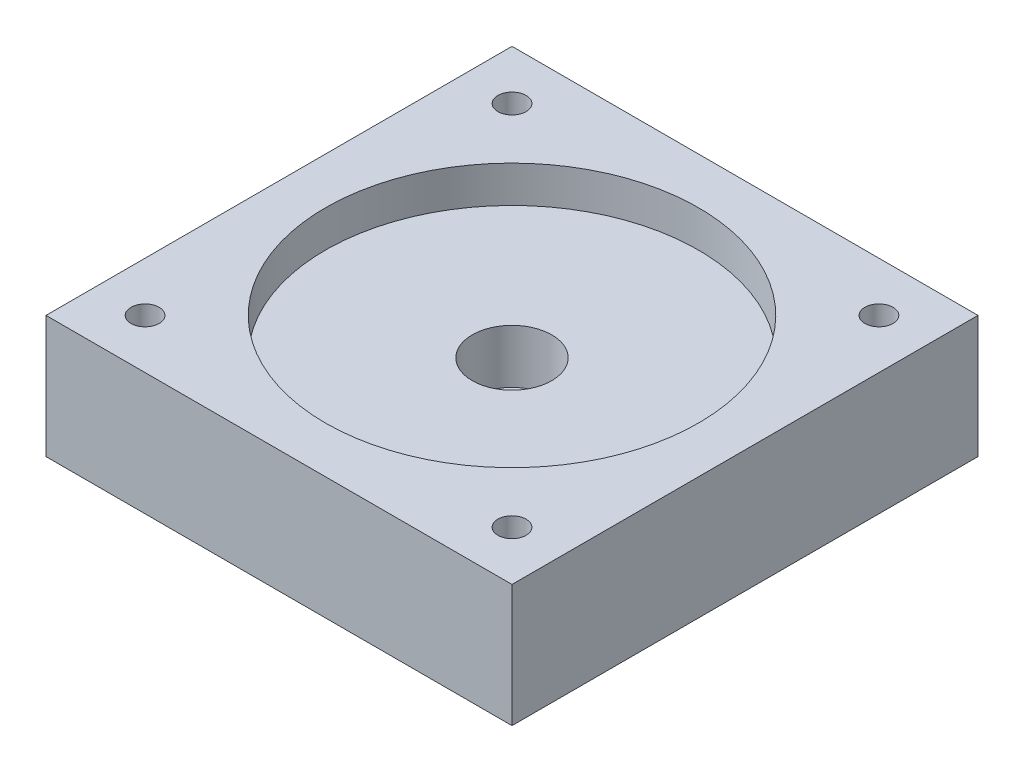
SolidWorks part; units mm, degrees
ref_plane "Front Plane" through (0, 0, 0) normal (0, 0, 1) x (1, 0, 0)
ref_plane "Top Plane" through (0, 0, 0) normal (0, 1, 0) x (1, 0, 0)
ref_plane "Right Plane" through (0, 0, 0) normal (1, 0, 0) x (0, 0, -1)
sketch "Sketch1" plane through (0, 0, 0) normal (0, 1, 0) x (1, 0, 0)
  line L1 (-19.05, 19.05) -> (19.05, 19.05)
  line L2 (-19.05, 19.05) -> (-19.05, -19.05)
  line L3 (-19.05, -19.05) -> (19.05, -19.05)
  line L4 (19.05, 19.05) -> (19.05, -19.05)
  circle A0 centre (0, 0) radius 1.75
  circle A1 centre (0, 0) radius 15.25
  circle A2 centre (0, 0) radius 3.25
  circle A3 centre (-15, 15) radius 1.15
  circle A4 centre (15, 15) radius 1.15
  circle A5 centre (-15, -15) radius 1.15
  circle A6 centre (15, -15) radius 1.15
  dimension "D3" = 19.05
  dimension "D11" = 4.05
  dimension "D1" = 38.1
  dimension "D2" = 38.1
  dimension "D4" = 19.05
  dimension "D5" = 4.05
  dimension "D6" = 4.05
  dimension "D7" = 4.05
  dimension "D8" = 4.05
  dimension "D9" = 4.05
  dimension "D10" = 4.05
  dimension "D12" = 4.05
extrude "Boss-Extrude1" add sketch "Sketch1" against normal blind 10 contours L3 L4 L1 L2
extrude "Cut-Extrude1" cut sketch "Sketch1<3>" against normal blind 10 contours A3 region at (-15, 0, -15)
sketch "Sketch1<3>" plane through (0, 0, 0) normal (0, 1, 0) x (1, 0, 0) same geometry as "Sketch1"
extrude "Cut-Extrude2" cut sketch "Sketch1<4>" against normal blind 10 contours A4 region at (15, 0, -15)
sketch "Sketch1<4>" plane through (0, 0, 0) normal (0, 1, 0) x (1, 0, 0) same geometry as "Sketch1"
extrude "Cut-Extrude3" cut sketch "Sketch1<5>" against normal blind 10 contours A5 region at (-15, 0, 15)
sketch "Sketch1<5>" plane through (0, 0, 0) normal (0, 1, 0) x (1, 0, 0) same geometry as "Sketch1"
extrude "Cut-Extrude4" cut sketch "Sketch1<6>" against normal blind 10 contours A6 region at (15, 0, 15)
sketch "Sketch1<6>" plane through (0, 0, 0) normal (0, 1, 0) x (1, 0, 0) same geometry as "Sketch1"
extrude "Cut-Extrude5" cut sketch "Sketch1<7>" against normal blind 3 contours A1 A2 region at (-14.8187, 0, 0)
sketch "Sketch1<7>" plane through (0, 0, 0) normal (0, 1, 0) x (1, 0, 0) same geometry as "Sketch1"
extrude "Cut-Extrude6" cut sketch "Sketch1<8>" against normal blind 7.4 contours A2 A0 region at (-3.1581, 0, 0)
sketch "Sketch1<8>" plane through (0, 0, 0) normal (0, 1, 0) x (1, 0, 0) same geometry as "Sketch1"
extrude "Cut-Extrude7" cut sketch "Sketch1<9>" against normal blind 10 contours A0 region at (0, 0, 0)
sketch "Sketch1<9>" plane through (0, 0, 0) normal (0, 1, 0) x (1, 0, 0) same geometry as "Sketch1"
